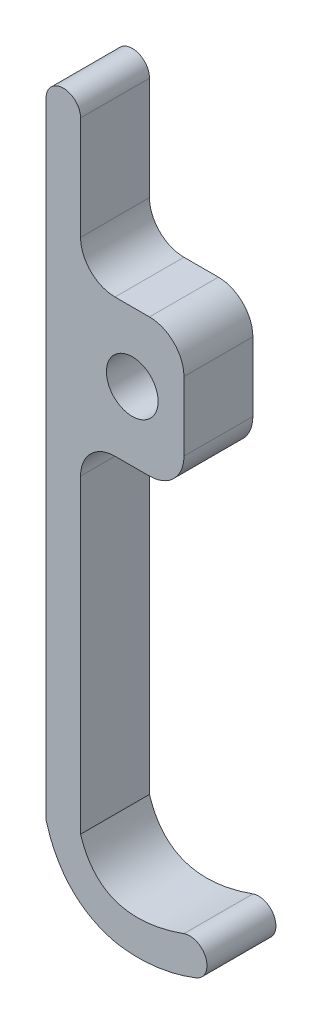
SolidWorks part; units mm, degrees
ref_plane "Alzado" through (0, 0, 0) normal (0, 0, 1) x (1, 0, 0)
ref_plane "Planta" through (0, 0, 0) normal (0, 1, 0) x (1, 0, 0)
ref_plane "Vista lateral" through (0, 0, 0) normal (1, 0, 0) x (0, 0, -1)
sketch "Croquis1" plane through (0, 0, 0) normal (0, 0, 1) x (1, 0, 0)
  line L0 (0, 0) -> (0, -18)
  line L1 (-1, 0) -> (-1, -18.1551)
  arc A0 (0, 0) -> (-1, 0) centre (-0.5, 0) ccw
  arc A1 (3, -19) -> (3.3369, -19.9416) centre (3.1684, -19.4708) cw
  spline S0 degree 2 poles (0, -18) (0.5915, -19.8617) (3, -19) knots 0 0 0 1 1 1
  spline S1 degree 1 poles (-1, -18.1551) (3.3369, -19.9416) knots 0 0 1 1 construction
  spline S2 degree 2 poles (-1, -18.1551) (-0.9759, -18.2327) (-0.8994, -18.4664) (-0.7561, -18.8178) (-0.4549, -19.3179) (0.028, -19.7929) (0.7773, -20.1973) (2.2762, -20.3524) (3.3369, -19.9416) knots -0.039688 -0.039688 -0.039688 0.009047 0.057783 0.155253 0.285214 0.415175 0.610117 1 1 1
  dimension "D2" = 3
  dimension "D4" = 0.75
  dimension "D1" = 18
  dimension "D3" = 1
  dimension "D5" = 0.4
  dimension "D6" = 1
extrude "Saliente-Extruir1" add sketch "Croquis1" along normal blind 2
sketch "Croquis2" plane through (0, 0, 0) normal (1, 0, 0) x (0, 0, -1)
  line L0 (0, 0) -> (0, 0.5) construction
  line L1 (-2, 0.5) -> (-2, 0) construction
  line L2 (0, 0.5) -> (-2, 0.5) construction
  line L3 (0, 0) -> (0, 0.5)
  line L4 (0, -18) -> (0, 0)
  line L5 (0, 0) -> (-2, 0)
  line L6 (-2, 0) -> (-2, -18)
  line L7 (-2, -18) -> (0, -18)
  line L8 (0, -18) -> (0, 0)
  line L9 (0, 0) -> (-2, 0)
  line L10 (-2, 0) -> (-2, -18)
  line L11 (-2, -18) -> (0, -18)
  line L12 (-2, 0.5) -> (-2, 0)
  line L13 (0, 0.5) -> (-2, 0.5)
  line L15 (-2, 0.5) -> (0, 0.5)
  line L16 (-2, 0.5) -> (-2, -1)
  line L17 (-2, -1) -> (0, -1)
  line L18 (0, 0.5) -> (0, -1)
  dimension "D2" = 1.5
  dimension "D1" = 0
sketch "Croquis3" plane through (0, 0, 0) normal (0, 0, -1) x (-1, 0, 0)
  line L0 (0, -18) -> (0, -4) construction
  line L1 (0, 0) -> (0, -18) construction
  line L2 (-3, -4) -> (0, -8) construction
  line L3 (0, -4) -> (-3, -4)
  line L4 (0, -4) -> (0, -8)
  line L5 (0, -8) -> (-3, -8)
  line L6 (-3, -4) -> (-3, -8)
  circle A0 centre (-1.5, -6) radius 0.75
  dimension "D4" = 1.5
  dimension "D1" = 14
  dimension "D2" = 3
  dimension "D3" = 4
extrude "Saliente-Extruir2" add sketch "Croquis3" against normal up to surface (2 mm away) up to face at (0.6899, -12.3392, 2)
fillet "Redondeo1" radius 1 4 edges at (3, -4, 1) (3, -8, 1) (0, -8, 1) (0, -4, 1)
